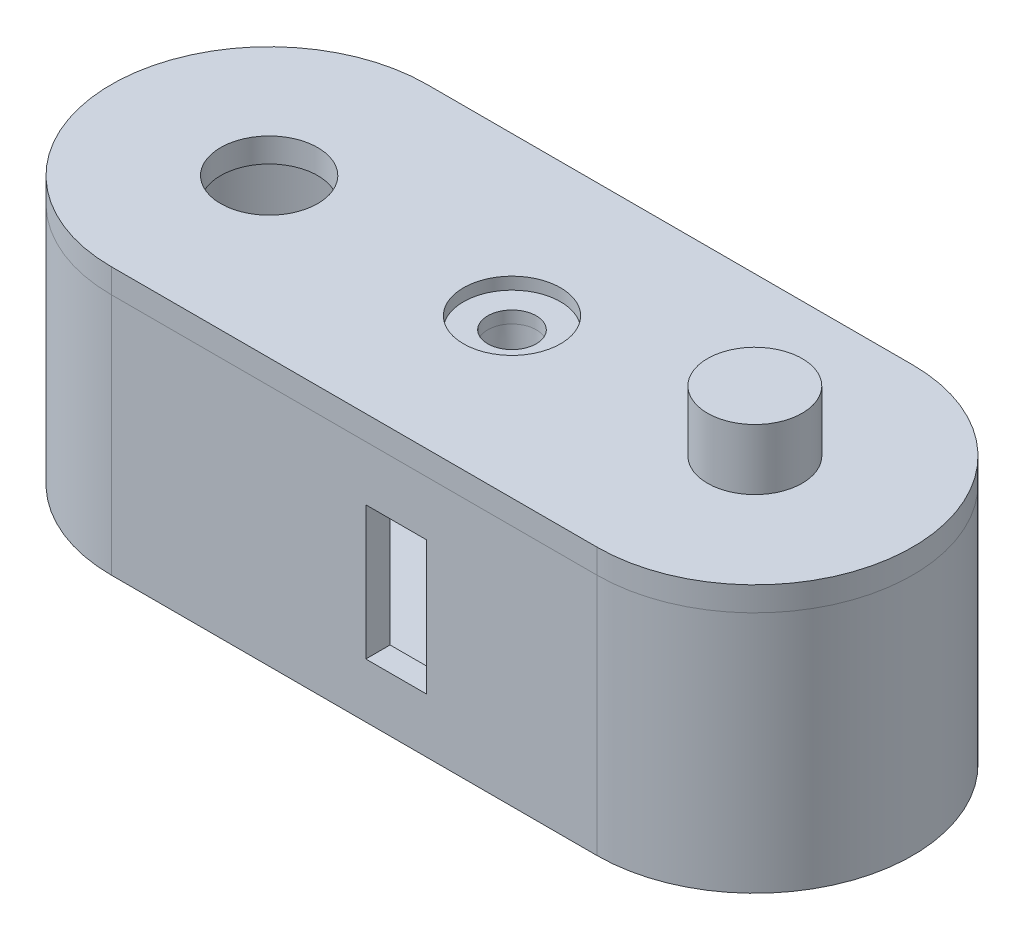
SolidWorks part; units mm, degrees
ref_plane "Front Plane" through (0, 0, 0) normal (0, 0, 1) x (1, 0, 0)
ref_plane "Top Plane" through (0, 0, 0) normal (0, 1, 0) x (1, 0, 0)
ref_plane "Right Plane" through (0, 0, 0) normal (1, 0, 0) x (0, 0, -1)
sketch "Sketch1" plane through (0, 0, 0) normal (0, 1, 0) x (1, 0, 0)
  line L0 (0, 0) -> (40, 0) construction
  line L1 (0, 11) -> (40, 11)
  line L2 (0, -11) -> (40, -11)
  line L3 (0, 0) -> (40, 0) construction
  line L4 (0, 13) -> (40, 13)
  line L5 (0, -13) -> (40, -13)
  arc A0 (0, 11) -> (0, -11) centre (0, 0) ccw
  arc A1 (40, -11) -> (40, 11) centre (40, 0) ccw
  arc A2 (0, 13) -> (0, -13) centre (0, 0) ccw
  arc A3 (40, -13) -> (40, 13) centre (40, 0) ccw
  point P3 (20, 0)
  point P8 (20, 0)
  dimension "D3" = 11
  dimension "D1" = 2
  dimension "D2" = 40
extrude "Boss-Extrude1" add sketch "Sketch1" along normal blind 20
sketch "Sketch2" plane through (0, 0, 0) normal (0, -1, 0) x (1, 0, 0)
  line L0 (0, 11) -> (40, 11) construction
  line L1 (20, 11) -> (0, 11)
  line L3 (20, -11) -> (0, -11)
  line L6 (20, 11) -> (40, 11)
  line L8 (20, -11) -> (40, -11)
  arc A0 (0, 11) -> (0, -11) centre (0, 0) ccw
  arc A1 (40, -11) -> (40, 11) centre (40, 0) ccw construction
  arc A2 (40, -11) -> (40, 11) centre (40, 0) ccw
  circle A3 centre (40, 0) radius 4
  dimension "D1" = 8
extrude "Boss-Extrude2" add sketch "Sketch2" against normal blind 4
sketch "Sketch3" plane through (0, 4, 0) normal (0, 1, 0) x (1, 0, 0)
  circle A0 centre (0, 0) radius 8.9358
  circle A1 centre (0, 0) radius 11
extrude "Boss-Extrude3" add sketch "Sketch3" along normal blind 4
sketch "Sketch4" plane through (0, 4, 0) normal (0, 1, 0) x (1, 0, 0)
  line L0 (20, -11) -> (20, 11) construction
  line L1 (0, -11) -> (40, -11) construction
  line L2 (40, 11) -> (0, 11) construction
  line L3 (51, 0) -> (-11, 0) construction
  arc A0 (40, -11) -> (40, 11) centre (40, 0) ccw construction
  arc A1 (0, 11) -> (0, -11) centre (0, 0) ccw construction
  circle A2 centre (20, 0) radius 3
  dimension "D1" = 6
extrude "Boss-Extrude4" add sketch "Sketch4" along normal up to surface (16 mm away) up to face at (20, 20, 0)
sketch "Sketch5" plane through (0, 20, 0) normal (0, 1, 0) x (1, 0, 0)
  circle A0 centre (20, 0) radius 2
  dimension "D1" = 4
extrude "Cut-Extrude1" cut sketch "Sketch5" against normal blind 6 draft 2
sketch "Sketch6" plane through (0, 20, 0) normal (0, 1, 0) x (1, 0, 0)
  line L0 (0, 0) -> (40, 0) construction
  line L1 (0, 13) -> (40, 13)
  line L2 (0, -13) -> (40, -13)
  line L3 (0, 0) -> (40, 0) construction
  arc A0 (0, 13) -> (0, -13) centre (0, 0) ccw
  arc A1 (40, -13) -> (40, 13) centre (40, 0) ccw
  circle A4 centre (0, 0) radius 4
  point P4 (20, 0)
  point P9 (20, 0)
  dimension "D1" = 13
  dimension "D2" = 8
extrude "Boss-Extrude5" add sketch "Sketch6" along normal blind 2 separate body
sketch "Sketch7" plane through (0, 22, 0) normal (0, 1, 0) x (1, 0, 0)
  circle A0 centre (20, 0) radius 2
  dimension "D1" = 4
extrude "Cut-Extrude2" cut sketch "Sketch7" against normal blind 2
sketch "Sketch8" plane through (0, 22, 0) normal (0, 1, 0) x (1, 0, 0)
  circle A0 centre (20, 0) radius 4
  circle A1 centre (20, 0) radius 2 construction
  dimension "D1" = 2
extrude "Cut-Extrude3" cut sketch "Sketch8" against normal blind 1
sketch "Sketch9" plane through (0, 20, 0) normal (0, -1, 0) x (1, 0, 0)
  circle A1 centre (40, 0) radius 8.7908
  circle A2 centre (40, 0) radius 10.1726
extrude "Boss-Extrude6" add sketch "Sketch9" along normal blind 7
sketch "Sketch10" plane through (0, 20, 0) normal (0, -1, 0) x (1, 0, 0)
  circle A0 centre (40, 0) radius 8.7908
extrude "Boss-Extrude7" add sketch "Sketch10" along normal blind 4
sketch "Sketch11" plane through (0, 0, 0) normal (0, -1, 0) x (1, 0, 0)
  circle A0 centre (0, 0) radius 3.9
  dimension "D1" = 7.8
extrude "Boss-Extrude8" add sketch "Sketch11" along normal blind 5
sketch "Sketch12" plane through (0, 22, 0) normal (0, 1, 0) x (1, 0, 0)
  circle A0 centre (40, 0) radius 3.9
  dimension "D1" = 7.8
extrude "Boss-Extrude9" add sketch "Sketch12" along normal blind 5
sketch "Sketch13" plane through (0, 0, 13) normal (0, 0, 1) x (1, 0, 0)
  line L0 (25.9599, 15.5) -> (25.9599, 4.5)
  line L1 (25.9599, 15.5) -> (20.9599, 15.5)
  line L2 (25.9599, 4.5) -> (20.9599, 4.5)
  line L3 (20.9599, 15.5) -> (20.9599, 4.5)
  line L4 (23.4599, 20) -> (23.4599, 0) construction
  line L7 (40, 10) -> (0, 10) construction
  point P8 (23.4599, 4.5)
  point P9 (20.9599, 10)
  dimension "D1" = 5
  dimension "D2" = 11
extrude "Cut-Extrude4" cut sketch "Sketch13" against normal blind 2
sketch "Sketch14" plane through (0, 0, -13) normal (0, 0, -1) x (-1, 0, 0)
  line L1 (-25.9599, 15.5) -> (-20.9599, 15.5)
  line L2 (-25.9599, 15.5) -> (-25.9599, 4.5)
  line L3 (-25.9599, 4.5) -> (-20.9599, 4.5)
  line L4 (-20.9599, 15.5) -> (-20.9599, 4.5)
extrude "Cut-Extrude5" cut sketch "Sketch14" against normal blind 2
